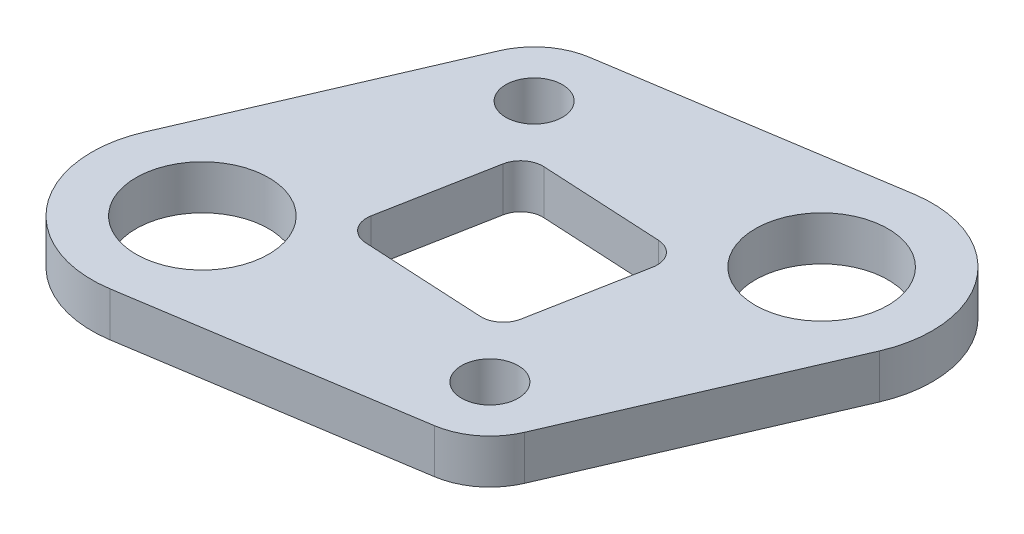
SolidWorks part; units mm, degrees
ref_plane "Front Plane" through (0, 0, 0) normal (0, 0, 1) x (1, 0, 0)
ref_plane "Top Plane" through (0, 0, 0) normal (0, 1, 0) x (1, 0, 0)
ref_plane "Right Plane" through (0, 0, 0) normal (1, 0, 0) x (0, 0, -1)
sketch "Sketch1" plane through (0, 0, 0) normal (0, 1, 0) x (1, 0, 0)
  line L0 (0, 0) -> (20.6375, 0) construction
  line L1 (20.6375, 0) -> (25.4, 19.05) construction
  line L2 (25.4, 19.05) -> (4.7625, 19.05) construction
  line L3 (4.7625, 19.05) -> (0, 0) construction
  line L8 (0.3898, 20.9369) -> (-7.2879, 3.1449)
  line L9 (4.0298, 23.7558) -> (24.1788, 26.893)
  line L10 (32.6879, 15.9051) -> (25.0102, -1.8869)
  line L11 (1.2212, -7.843) -> (21.3702, -4.7058)
  line L12 (0, 0) -> (25.4, 19.05) construction
  line L13 (4.7625, 19.05) -> (20.6375, 0) construction
  line L14 (7.5279, 4.1904) -> (16.2024, 3.7319)
  line L15 (17.8461, 5.0227) -> (19.3482, 12.9798)
  line L16 (17.8721, 14.8596) -> (9.1976, 15.3181)
  line L17 (7.5539, 14.0273) -> (6.0518, 6.0702)
  circle A0 centre (0, 0) radius 4.7625
  circle A1 centre (25.4, 19.05) radius 4.7625
  circle A2 centre (20.6375, 0) radius 2.032
  circle A3 centre (4.7625, 19.05) radius 2.032
  arc A4 (-7.2879, 3.1449) -> (1.2212, -7.843) centre (0, 0) ccw
  arc A5 (4.0298, 23.7558) -> (0.3898, 20.9369) centre (4.7625, 19.05) ccw
  arc A6 (32.6879, 15.9051) -> (24.1788, 26.893) centre (25.4, 19.05) ccw
  arc A7 (21.3702, -4.7058) -> (25.0102, -1.8869) centre (20.6375, 0) ccw
  arc A8 (7.5279, 4.1904) -> (6.0518, 6.0702) centre (7.6117, 5.7757) cw
  arc A9 (16.2024, 3.7319) -> (17.8461, 5.0227) centre (16.2862, 5.3172) ccw
  arc A10 (19.3482, 12.9798) -> (17.8721, 14.8596) centre (17.7883, 13.2743) ccw
  arc A11 (9.1976, 15.3181) -> (7.5539, 14.0273) centre (9.1138, 13.7328) ccw
  point P11 (8.2848, 14.8232)
  point P22 (0, 0)
  point P25 (5.715, 4.2863)
  point P28 (17.5886, 3.6587)
  point P31 (19.685, 14.7637)
  point P34 (7.8114, 15.3913)
  dimension "D4" = 9.525
  dimension "D5" = 4.064
  dimension "D6" = 7.9375
  dimension "D7" = 4.7625
  dimension "D12" = 1.5875
  dimension "D1" = 20.6375
  dimension "D2" = 19.05
  dimension "D3" = 4.7625
  dimension "D8" = 7.1437
  dimension "D9" = 7.1437
  dimension "D10" = 4.7625
  dimension "D11" = 4.7625
extrude "Boss-Extrude1" add sketch "Sketch1" along normal blind 3.175
equation "\"D9@Sketch1\"=\"D8@Sketch1\""
equation "\"D11@Sketch1\"=\"D10@Sketch1\""
